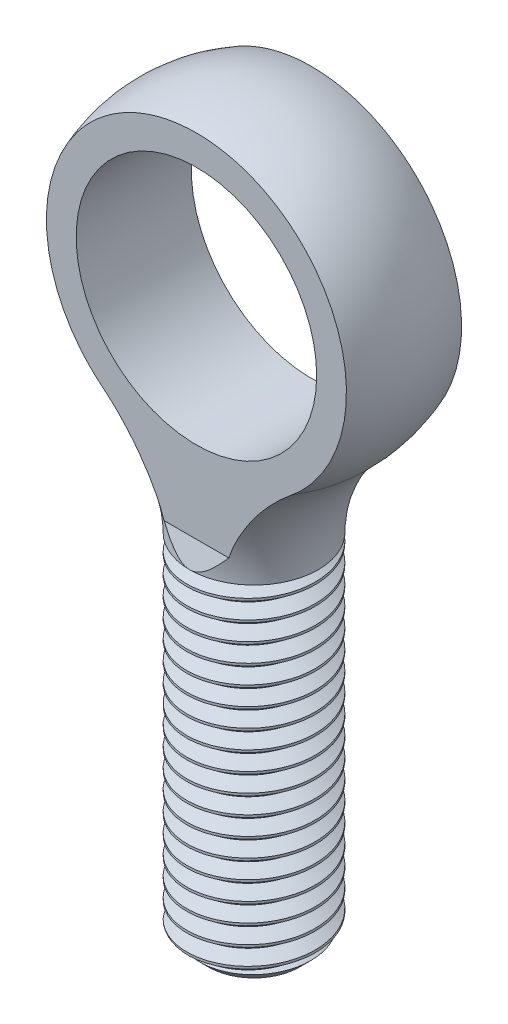
SolidWorks part; units mm, degrees
ref_plane "Front" through (0, 0, 0) normal (0, 0, 1) x (1, 0, 0)
ref_plane "Top" through (0, 0, 0) normal (0, 1, 0) x (1, 0, 0)
ref_plane "Right" through (0, 0, 0) normal (1, 0, 0) x (0, 0, -1)
sketch "Sketch1" plane through (0, 0, 0) normal (0, 0, 1) x (1, 0, 0)
  line L0 (0, 0) -> (0, -33)
  line L1 (0, -33) -> (6, -33)
  line L2 (6, -33) -> (6, 0)
  line L3 (6, 0) -> (0, 0)
  line L5 (0, 36) -> (0, 0) construction
  line L6 (0, 36) -> (15, 36) construction
  line L7 (15, 36) -> (15, 21) construction
  line L8 (-6, -33) -> (-6, 0) construction
  arc A0 (10.3448, 10.1379) -> (0, 36) centre (0, 21) ccw construction
  circle A1 centre (0, 21) radius 6 construction
  circle A2 centre (0, 21) radius 11.115 construction
  circle A3 centre (0, 21) radius 11.2262 construction
  arc A4 (6, 0) -> (10.3448, 10.1379) centre (20, 0) cw construction
  point P16 (-6, -22.9375)
  dimension "A" = 12
  dimension "Ball Dia" = 22.23
  dimension "B" = 30
  dimension "D1" = 22.4523
  dimension "D" = 54
  dimension "E" = 33
  dimension "Thread Dia" = 12
  dimension "D2" = 10.0625
revolve "Revolve1" add sketch "Sketch1" angle 360 about L5
sketch "Sketch12" plane through (0, -33, 0) normal (0, -1, 0) x (1, 0, 0)
  circle A1 centre (0, 0) radius 6
  circle A2 centre (0, 0) radius 6
  dimension "D1" = 0
curve "Helix/Spiral1" pitch 1.75 height 34.75 turns 19.8571 parameters "pitch"=1.75
chamfer "Chamfer2" distance 1.75 angle 45 1 edges at (-6, -33, 0)
sketch "Sketch13" plane through (0, 0, 0) normal (1, 0, 0) x (0, 0, -1)
  line L0 (-6, -34.5312) -> (-6, -33)
  line L1 (-6, -33) -> (-4.8633, -33.6562)
  line L2 (-4.8633, -33.6562) -> (-4.8633, -33.875)
  line L3 (-4.8633, -33.875) -> (-6, -34.5312)
  line L4 (-4.8633, -33.7656) -> (-6, -33.7656) construction
  line L5 (-5.4317, -34.2031) -> (-5.4317, -33.3281) construction
  line L6 (-6, -33) -> (6, -33) construction
  dimension "D1" = 60
  dimension "D3" = 0.875
sweep "Cut-Sweep1" cut profiles "Sketch13" path "Helix/Spiral1" align with end faces yes
sketch "Sketch4" plane through (0, 0, 0) normal (0, 0, 1) x (1, 0, 0)
  line L0 (6, 0) -> (0, 0) construction
  line L2 (0, 36) -> (0, 0) construction
  line L3 (6, 0) -> (0, 0)
  line L5 (0, 36) -> (0, 0)
  line L6 (0, 36) -> (0, 38.54) construction
  arc A0 (10.3448, 10.1379) -> (0, 36) centre (0, 21) ccw construction
  arc A1 (10.3448, 10.1379) -> (0, 36) centre (0, 21) ccw
  arc A2 (10.3448, 10.1379) -> (6, 0) centre (20, 0) ccw construction
  arc A3 (10.3448, 10.1379) -> (6, 0) centre (20, 0) ccw
  dimension "D1" = 2.54
revolve "Revolve2" add sketch "Sketch4" angle 360 about L6
sketch "Sketch5" plane through (0, 0, 0) normal (1, 0, 0) x (0, 0, -1)
  line L0 (5.375, 36) -> (15, 36)
  line L1 (-5.375, 36) -> (5.375, 36) construction
  line L2 (-5.375, 36) -> (-5.375, 2.15)
  line L3 (-6, 0) -> (6, 0) construction
  line L4 (5.375, 36) -> (5.375, 2.15)
  line L5 (15, 36) -> (15, 0)
  line L6 (15, 0) -> (6, 0)
  line L7 (-6, 0) -> (-15, 0)
  line L8 (-15, 0) -> (-15, 36)
  line L9 (-15, 36) -> (-5.375, 36)
  line L10 (6, 0) -> (5.375, 2.15)
  line L11 (-6, 0) -> (-5.375, 2.15)
  line L12 (-5.375, 2.15) -> (5.375, 2.15) construction
  line L13 (0, 0) -> (0, 2.15) construction
  arc A0 (10.3448, 10.1379) -> (-10.3448, 10.1379) centre (0, 21) ccw construction
  dimension "F" = 10.75
  dimension "D2" = 2.15
  dimension "D1" = 12
extrude "Cut-Extrude1" cut sketch "Sketch5" against normal through all and the other way through all
sketch "Sketch6" plane through (0, 0, 0) normal (0, 0, 1) x (1, 0, 0)
  circle A0 centre (0, 21) radius 11.2261 construction
  circle A1 centre (0, 21) radius 11.2261
extrude "Cut-Extrude2" cut sketch "Sketch6" against normal through all and the other way through all
equation "\"D1@Sketch1\"=\"Ball Dia@Sketch1\"*1.01"
equation "\"D1@Sketch5\"=\"Thread Dia@Sketch1\""
equation "\"D2@Sketch5\"=\"F@Sketch5\"/5"
equation "\"D2@Sketch13\" = \"pitch@Helix/Spiral1\"*.125"
equation "\"D3@Sketch13\" = \"pitch@Helix/Spiral1\"*.50"
equation "\"D3@Helix/Spiral1\" = \"E@Sketch1\"+\"pitch@Helix/Spiral1\""
equation "\"D1@Chamfer2\" = \"pitch@Helix/Spiral1\""
equation "\"D2@Sketch1\" = \"pitch@Helix/Spiral1\"*5.75"
